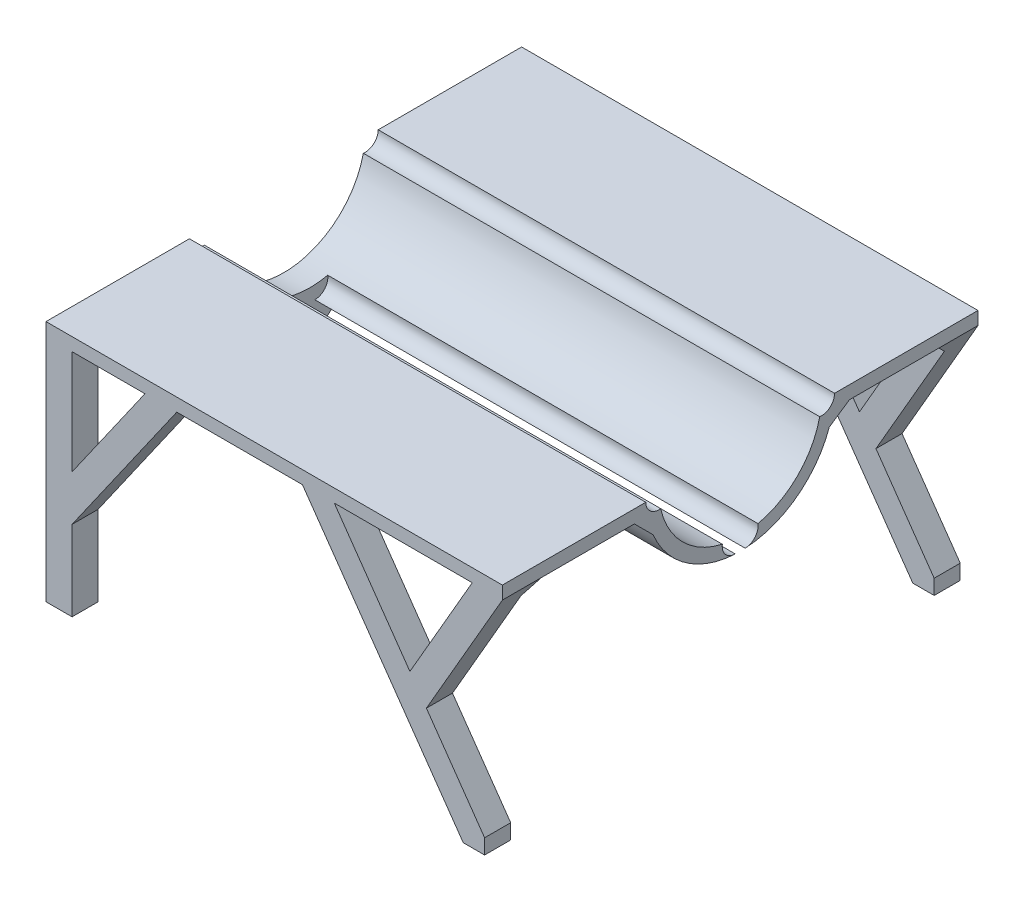
SolidWorks part; units mm, degrees
ref_plane "Front Plane" through (0, 0, 0) normal (0, 0, 1) x (1, 0, 0)
ref_plane "Top Plane" through (0, 0, 0) normal (0, 1, 0) x (1, 0, 0)
ref_plane "Right Plane" through (0, 0, 0) normal (1, 0, 0) x (0, 0, -1)
sketch "Sketch1" plane through (0, 0, 0) normal (1, 0, 0) x (0, 0, -1)
  line L0 (-87.8601, 0) -> (97.8786, 0) construction
  line L1 (-39.616, -2.3812) -> (-115.816, -2.3813)
  line L2 (0, -100.4363) -> (0, 110.3288) construction
  line L3 (39.616, -2.3812) -> (115.816, -2.3813)
  line L4 (-2.413, -39.6141) -> (-2.413, -100.4363) construction
  line L5 (2.413, -39.6141) -> (2.413, -100.4363) construction
  line L6 (-45.202, -8.7312) -> (-115.816, -8.7313)
  line L7 (45.202, -8.7312) -> (115.816, -8.7312)
  line L8 (-115.816, -2.3813) -> (-115.816, -8.7313)
  line L9 (115.816, -2.3813) -> (115.816, -8.7312)
  line L11 (-2.7991, -45.9523) -> (-2.413, -45.9523)
  line L12 (-2.413, -45.9523) -> (-2.413, -39.6141)
  line L13 (2.7991, -45.9523) -> (2.413, -45.9523)
  line L14 (2.413, -45.9523) -> (2.413, -39.6141)
  circle A0 centre (0, 0) radius 39.6875 construction
  arc A1 (-39.616, -2.3812) -> (-2.413, -39.6141) centre (0, 0) ccw
  arc A2 (39.616, -2.3812) -> (2.413, -39.6141) centre (0, 0) cw
  arc A3 (-45.966, -2.3813) -> (-38.7291, -8.669) centre (-39.616, -2.3812) ccw
  arc A4 (45.966, -2.3813) -> (38.7291, -8.669) centre (39.616, -2.3812) cw
  arc A5 (-45.202, -8.7312) -> (-2.7991, -45.9523) centre (0, 0) ccw
  arc A6 (45.202, -8.7312) -> (2.7991, -45.9523) centre (0, 0) cw
  dimension "D1" = 79.375
  dimension "D5" = 6.35
  dimension "D8" = 2.7991
  dimension "D2" = 185.7387
  dimension "D3" = 2.3813
  dimension "D4" = 2.413
  dimension "D6" = 76.2
  dimension "D7" = 6.35
extrude "Boss-Extrude1" add sketch "Sketch1" along normal blind 222.25 contours L6 A5 L11 L12 A1 A3 L1 L8 | A6 L7 L9 L3 A4 A2 L14 L13 region at (0, -8.0917, 44.5776) region at (0, -3.5961, -80.891)
chamfer "Chamfer1" distance 6.35 angle 45 1 edges at (111.125, -8.7312, 45.202) first distance on face at (111.125, -8.7313, 80.509)
chamfer "Chamfer2" distance 6.35 angle 45 1 edges at (111.125, -8.7312, -45.202) first distance on face at (111.125, -30.9703, -27.1856)
sketch "Sketch2" plane through (0, 0, 0) normal (-1, 0, 0) x (0, 0, 1)
  line L0 (0, -38.0235) -> (0, -120.5735) construction
  line L1 (-152.5028, -120.5735) -> (152.2972, -120.5735) construction
  line L2 (-103.116, -8.7312) -> (-103.116, -120.5735)
  line L3 (-115.816, -8.7312) -> (-103.116, -8.7312)
  line L4 (-115.816, -8.7312) -> (-115.816, -120.5735)
  line L5 (-115.816, -120.5735) -> (-103.116, -120.5735)
  line L7 (115.816, -8.7312) -> (103.116, -8.7312)
  line L8 (115.816, -8.7312) -> (115.816, -120.5735)
  line L9 (115.816, -120.5735) -> (103.116, -120.5735)
  line L10 (103.116, -8.7312) -> (103.116, -120.5735)
  dimension "D1" = 82.55
  dimension "D2" = 304.8
  dimension "D3" = 152.5028
  dimension "D4" = 12.7
  dimension "D5" = 0
extrude "Boss-Extrude2" add sketch "Sketch2" against normal blind 12.7
sketch "Sketch3" plane through (222.25, 0, 0) normal (1, 0, 0) x (0, 0, -1)
  line L0 (-16.7727, -35.9691) -> (0, 0) construction
  line L1 (0, 0) -> (16.7727, -35.9691) construction
  line L2 (0, 0) -> (-45.966, 0) construction
  line L3 (-45.966, 0) -> (-45.966, -2.3813) construction
  line L4 (-16.7727, -35.9691) -> (-19.4563, -41.7241)
  line L5 (16.7727, -35.9691) -> (19.4563, -41.7241)
  line L6 (0, -46.0375) -> (0, -58.7375) construction
  arc A0 (-16.7727, -35.9691) -> (16.7727, -35.9691) centre (0, 0) ccw
  arc A1 (-38.7291, -8.669) -> (-2.413, -39.6141) centre (0, 0) ccw construction
  arc A2 (-19.4563, -41.7241) -> (19.4563, -41.7241) centre (0, 0) ccw
  spline S0 degree 3 poles (-19.4563, -41.7241) (-13.1274, -51.7966) (-8.4146, -58.658) (0, -58.7375) knots 0 0 0 0 1 1 1 1
  spline S1 degree 3 poles (19.4563, -41.7241) (13.1274, -51.7966) (8.4146, -58.658) (0, -58.7375) knots 0 0 0 0 1 1 1 1
  arc M5 (2.7991, -45.9523) -> (43.3947, -15.3737) centre (0, 0) ccw
  arc M11 (38.7291, -8.669) -> (2.413, -39.6141) centre (0, 0) cw
  line M12 (2.413, -39.6141) -> (2.413, -45.9523)
  line M13 (2.413, -45.9523) -> (2.7991, -45.9523)
  dimension "D4" = 12.7
  dimension "D1" = 65
  dimension "D2" = 50
  dimension "D3" = 6.35
extrude "Boss-Extrude3" add sketch "Sketch3" along normal blind 12.7 contours S1 A2 S0 M5 | L4 A2 A0 M13 M12 | L5 M11 M12 M13 M5 region at (222.25, -41.7341, 8.028) region at (222.25, -50.3525, 0) region at (222.25, -41.406, -10.4087)
chamfer "Chamfer3" distance 19.05 angle 45 2 edges at (222.25, -38.8466, 18.1145) (222.25, -38.8466, -18.1145)
sketch "Sketch4" plane through (0, 0, 115.816) normal (0, 0, 1) x (1, 0, 0)
  line L0 (0, -120.5735) -> (203.2, -120.5735) construction
  line L1 (0, -120.5735) -> (0, -2.3813) construction
  line L2 (203.2, -120.5735) -> (124.8872, -8.7313)
  line L3 (222.25, -8.7313) -> (12.7, -8.7312) construction
  line L4 (222.25, -8.7313) -> (178.2501, -84.9413)
  line L5 (213.6032, -113.2891) -> (135.2904, -1.4468)
  line L6 (211.2515, -2.3813) -> (167.2516, -78.5913)
  line L7 (203.2, -120.5735) -> (213.6032, -113.2891)
  line L8 (124.8872, -8.7313) -> (135.2904, -1.4468)
  line L9 (222.25, -8.7313) -> (211.2515, -2.3813)
  line L10 (178.2501, -84.9413) -> (167.2516, -78.5913)
  line L11 (133.9559, -2.3813) -> (135.9447, -2.3813)
  line L12 (222.25, -2.3813) -> (0, -2.3813) construction
  line L13 (203.2, -120.5735) -> (213.6032, -120.5735)
  line L14 (213.6032, -120.5735) -> (213.6032, -113.2891)
  line L16 (63.6909, -8.7313) -> (12.7, -81.5539)
  line L17 (0, -8.7312) -> (222.25, -8.7312) construction
  line L18 (12.7, -120.5735) -> (12.7, -8.7312) construction
  line L19 (53.2877, -1.4468) -> (2.2968, -74.2694)
  line L20 (63.6909, -8.7313) -> (53.2877, -1.4468)
  line L21 (12.7, -81.5539) -> (2.2968, -74.2694)
  line M8 (12.7, -8.7312) -> (222.25, -8.7313)
  dimension "D1" = 55
  dimension "D2" = 203.2
  dimension "D3" = 60
  dimension "D5" = 35
  dimension "D6" = 88.9
  dimension "D4" = 12.7
  dimension "D7" = 12.7
extrude "Boss-Extrude4" add sketch "Sketch4" against normal blind 12.7 contours L6 L5 L2 M8 | L5 L6 L2 L4 | L6 L5 L4 M8 | L2 L7 L5 L4 | L13 L14 L7 | L21 L16 L19 M8 region at (31.8324, -43.3534, 115.816) region at (195.1699, -97.7993, 115.816) region at (210.1355, -118.1454, 115.816) region at (177.7346, -73.1342, 115.816) region at (152.9835, -38.1677, 115.816) region at (198.2639, -37.993, 115.816)
chamfer "Chamfer4" distance 6.35 angle 45 4 edges at (214.9177, -8.7313, 103.116) (132.6391, -8.7313, 103.116) (55.939, -8.7313, 103.116) (6.35, -8.7312, 103.116)
mirror "Mirror3" about plane through (0, 0, 0) normal (0, 0, 1) of "Boss-Extrude4"
chamfer "Chamfer5" distance 6.35 angle 45 4 edges at (6.35, -8.7312, -103.116) (55.939, -8.7313, -103.116) (132.6391, -8.7313, -103.116) (214.9177, -8.7313, -103.116)
sketch "Sketch5" plane through (0, -2.3812, 0) normal (0, 1, 0) x (1, 0, 0)
  line L0 (234.95, 0) -> (117.475, 0) construction
  line L1 (234.95, -22.3116) -> (234.95, 22.3116) construction
  line L2 (117.475, 0) -> (117.475, 73.3996) construction
  dimension "D1" = 117.475
  dimension "D2" = 73.3996
ref_plane "Plane1" through (117.475, 0, 0) normal (-1, 0, 0) x (0, 0, 1)
mirror "Mirror6" about plane through (117.475, 0, 0) normal (-1, 0, 0) of "Boss-Extrude3"
sketch "Sketch6" plane through (0, 0, 0) normal (0, 1, 0) x (1, 0, 0)
  line L1 (222.25, 115.816) -> (263.4622, 115.816)
  line L2 (222.25, 115.816) -> (222.25, -113.9576)
  line L3 (222.25, -113.9576) -> (263.4622, -113.9576)
  line L4 (263.4622, 115.816) -> (263.4622, -113.9576)
  dimension "D1" = 229.7736
  dimension "D2" = 41.2122
extrude "Cut-Extrude1" cut sketch "Sketch6" against normal blind 76.2
sketch "Sketch7" plane through (222.25, 0, 0) normal (1, 0, 0) x (0, 0, -1)
  line L0 (0, 0) -> (0, -80.9024) construction
  line L1 (-8.7001, -38.7222) -> (-2.413, -38.7222)
  line L2 (-2.413, -38.7222) -> (-2.413, -45.9523)
  line L3 (2.413, -38.7222) -> (2.413, -45.9523)
  line L4 (8.7001, -38.7222) -> (2.413, -38.7222)
  arc A0 (-2.413, -45.9523) -> (-8.6882, -38.7222) centre (-2.413, -39.6141) cw
  arc A1 (-38.7291, -8.669) -> (-2.413, -39.6141) centre (0, 0) ccw construction
  arc A2 (2.7991, -45.9523) -> (8.7001, -38.7222) centre (2.413, -39.6141) ccw
  arc A3 (2.413, -45.9523) -> (8.6882, -38.7222) centre (2.413, -39.6141) ccw
  line M10 (-2.413, -45.9523) -> (-2.413, -39.6141)
  arc M11 (-2.413, -39.6141) -> (-38.7291, -8.669) centre (0, 0) cw
extrude "Cut-Extrude2" cut sketch "Sketch7" against normal blind 209.55 contours A0 M10 M11 | L3 A3 L4 region at (222.25, -42.1034, 5.223) region at (222.25, -41.8291, -5.174)
